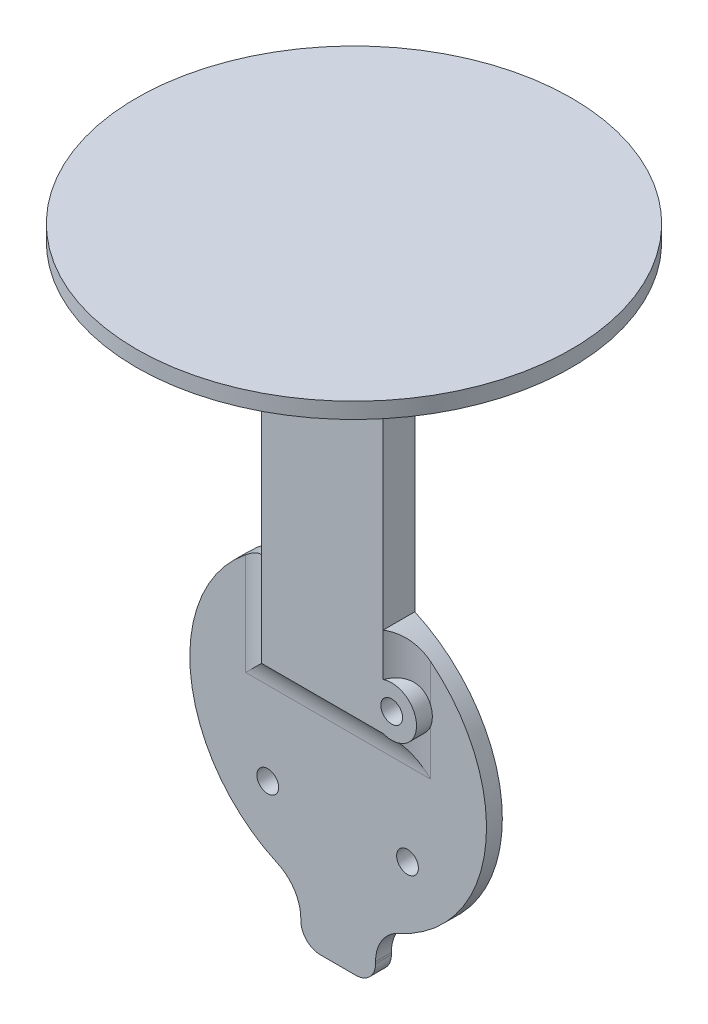
SolidWorks part; units mm, degrees
material "ABS"
ref_plane "Front Plane" through (0, 0, 0) normal (0, 0, 1) x (1, 0, 0)
ref_plane "Top Plane" through (0, 0, 0) normal (0, 1, 0) x (1, 0, 0)
ref_plane "Right Plane" through (0, 0, 0) normal (1, 0, 0) x (0, 0, -1)
sketch "Sketch2" plane through (0, 0, 0) normal (0, 0, 1) x (1, 0, 0)
  line L0 (-9.4483, -43.3361) -> (-9.4483, -43.8421)
  line L1 (-4.4483, -48.8421) -> (4.4483, -48.8421)
  line L2 (9.4483, -43.8421) -> (9.4483, -43.3361)
  circle A0 centre (17.5252, 17.4527) radius 2.75
  circle A1 centre (17.5252, -17.4739) radius 2.75
  arc A2 (-9.4483, -43.8421) -> (-4.4483, -48.8421) centre (-4.4483, -43.8421) ccw
  arc A3 (4.4483, -48.8421) -> (9.4483, -43.8421) centre (4.4483, -43.8421) ccw
  arc A4 (15.3539, -34.2127) -> (9.4483, -43.3361) centre (19.4483, -43.3361) ccw
  arc A5 (15.3539, -34.2127) -> (-15.3539, -34.2127) centre (0, 0) ccw
  arc A6 (-9.4483, -43.3361) -> (-15.3539, -34.2127) centre (-19.4483, -43.3361) ccw
  circle A7 centre (-17.8046, -17.4739) radius 2.75
  dimension "D1" = 5.5
  dimension "D2" = 5.5
  dimension "D3" = 5.5
extrude "Boss-Extrude2" add sketch "Sketch2" along normal blind 4 contours L0 A2 L1 A3 L2 A4 A5 A6
sketch "Sketch3" plane through (0, 0, 4) normal (0, 0, 1) x (1, 0, 0)
  line L0 (15.3729, 11.549) -> (-15.3729, 11.549)
  line L1 (15.3729, -32.5) -> (-15.3729, -32.5)
  line L2 (15.3729, -32.5) -> (15.3729, 107.5)
  line L3 (15.3729, 107.5) -> (-15.3729, 107.5)
  line L4 (-15.3729, -32.5) -> (-15.3729, 107.5)
  line L5 (15.3729, -32.5) -> (-15.3729, 107.5) construction
  line L6 (15.3729, 107.5) -> (-15.3729, -32.5) construction
  arc A0 (15.3539, -34.2127) -> (-15.3539, -34.2127) centre (0, 0) ccw construction
  point P3 (0, 37.5)
  arc M12 (15.3539, -34.2127) -> (-15.3539, -34.2127) centre (0, 0) ccw
  dimension "D1" = 140
extrude "Boss-Extrude3" add sketch "Sketch3" along normal blind 4 and the other way up to surface (4 mm away) contours L4 L0 L2 M12 | L4 L2 L3 M12 region at (0, 24.0044, 4) region at (0, 71.954, 4) other way up to face at (0, -33.635, 0)
fillet "Fillet1" radius 10 3 edges at (-15.3729, 22.8766, 4) (0, 11.549, 4) (15.3729, 22.8766, 4)
sketch "Sketch4" plane through (0, 107.5, 0) normal (0, 1, 0) x (1, 0, 0)
  line L0 (-15.3729, 0) -> (15.3729, 0) construction
  circle A0 centre (0, 0) radius 55
  dimension "D1" = 110
extrude "Boss-Extrude4" add sketch "Sketch4" along normal blind 4
fillet "Fillet2" radius 15 4 edges at (0, 107.5, 0) (-15.3729, 107.5, 4) (15.3729, 107.5, 4) (0, 107.5, 8)
extrude "Cut-Extrude1" cut sketch "Sketch2<4>" against normal through all both and the other way through all contours A7 | A1 | A0
sketch "Sketch2<4>" plane through (0, 0, 0) normal (0, 0, 1) x (1, 0, 0) same geometry as "Sketch2"
sketch "Sketch5" plane through (0, 0, 8) normal (0, 0, 1) x (1, 0, 0)
  circle A0 centre (17.5252, 17.4527) radius 6.2838
  circle A1 centre (17.5252, 17.4527) radius 2.75
extrude "Boss-Extrude5" add sketch "Sketch5" against normal up to surface (4 mm away) up to face at (-15.0546, -17.4739, 4)
